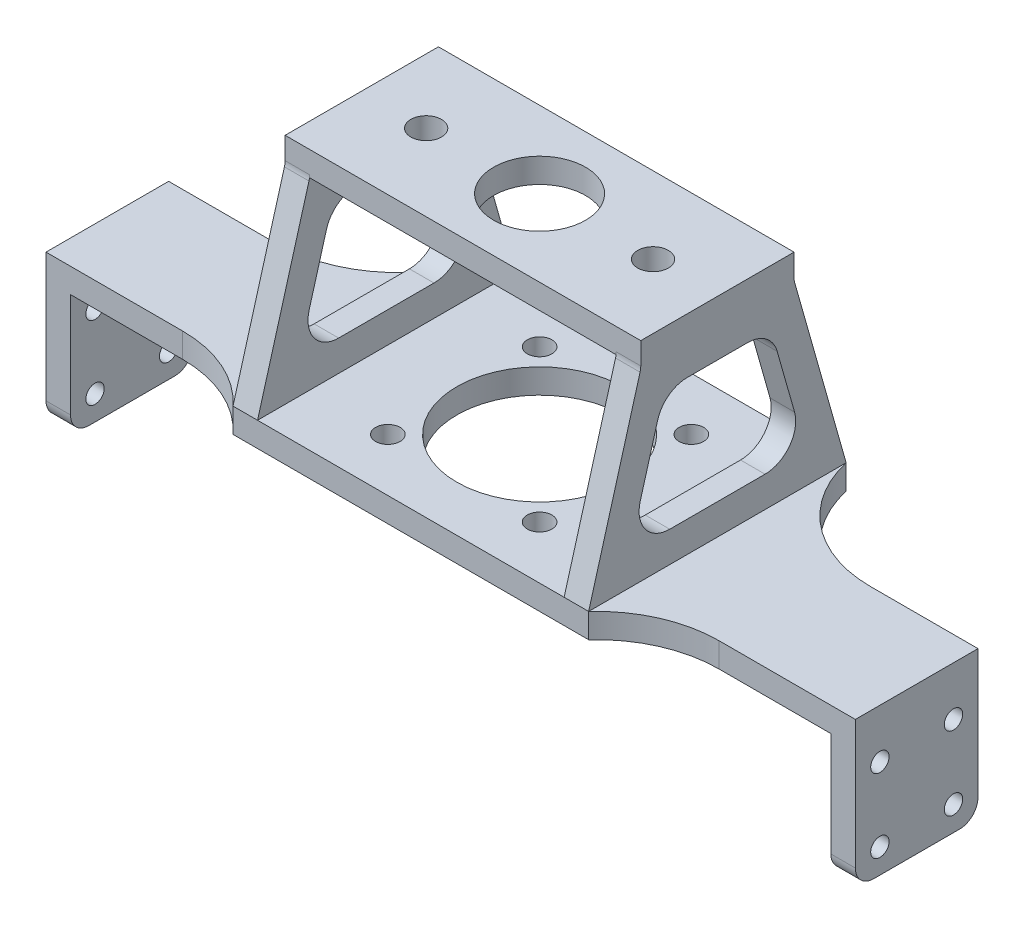
SolidWorks part; units mm, degrees
material "6061 合金"
ref_plane "前视基准面" through (0, 0, 0) normal (0, 0, 1) x (1, 0, 0)
ref_plane "上视基准面" through (0, 0, 0) normal (0, 1, 0) x (1, 0, 0)
ref_plane "右视基准面" through (0, 0, 0) normal (1, 0, 0) x (0, 0, -1)
sketch "草图1" plane through (0, 0, 0) normal (0, 1, 0) x (1, 0, 0)
  line L1 (-66, -21) -> (66, -21)
  line L2 (-66, -21) -> (-66, 21)
  line L3 (-66, 21) -> (66, 21)
  line L4 (66, -21) -> (66, 21)
  line L5 (-66, -21) -> (66, 21) construction
  line L6 (-66, 21) -> (66, -21) construction
  point P0 (0, 0)
  dimension "D1" = 132
  dimension "D2" = 42
extrude "凸台-拉伸1" add sketch "草图1" along normal blind 4
sketch "草图2" plane through (0, 4, 0) normal (0, 1, 0) x (1, 0, 0)
  line L0 (0, 0) -> (0, 17.5) construction
  line L1 (0, 0) -> (12.3744, 12.3744) construction
  circle A0 centre (0, 0) radius 17.5 construction
  circle A1 centre (12.3744, 12.3744) radius 2
  circle A2 centre (12.3744, -12.3744) radius 2
  circle A3 centre (-12.3744, -12.3744) radius 2
  circle A4 centre (-12.3744, 12.3744) radius 2
  circle A5 centre (0, 0) radius 13.5
  point P15 (0, 0)
  dimension "D1" = 35
  dimension "D2" = 4
  dimension "D5" = 27
  dimension "D3" = 45
  dimension "D4" = 4
extrude "切除-拉伸1" cut sketch "草图2" against normal blind 4
sketch "草图3" plane through (0, 4, 0) normal (0, 1, 0) x (1, 0, 0)
  line L0 (0, 21) -> (0, -21) construction
  line L1 (66, 21) -> (-66, 21) construction
  line L2 (-66, -21) -> (66, -21) construction
  line L3 (29, -21) -> (25, -21)
  line L4 (-29, 21) -> (-25, 21)
  line L5 (-29, 21) -> (-29, -21)
  line L6 (-29, -21) -> (-25, -21)
  line L7 (-25, 21) -> (-25, -21)
  line L8 (25, 21) -> (25, -21)
  line L9 (29, 21) -> (25, 21)
  line L10 (29, 21) -> (29, -21)
  dimension "D1" = 25
  dimension "D2" = 4
extrude "凸台-拉伸2" add sketch "草图3" along normal blind 30
sketch "草图4" plane through (0, 34, 0) normal (0, 1, 0) x (1, 0, 0)
  line L1 (-29, 21) -> (29, 21)
  line L2 (-29, 21) -> (-29, -21)
  line L3 (-29, -21) -> (29, -21)
  line L4 (29, 21) -> (29, -21)
extrude "凸台-拉伸3" add sketch "草图4" along normal blind 4
sketch "草图5" plane through (0, 0, 0) normal (0, -1, 0) x (1, 0, 0)
  line L0 (0, 21) -> (0, -21) construction
  line L1 (-66, 21) -> (66, 21) construction
  line L2 (66, -21) -> (-66, -21) construction
  line L3 (66, -21) -> (62, -21)
  line L8 (-66, 21) -> (-62, 21)
  line L9 (-66, 21) -> (-66, -21)
  line L10 (-66, -21) -> (-62, -21)
  line L11 (-62, 21) -> (-62, -21)
  line L12 (62, 21) -> (62, -21)
  line L13 (66, 21) -> (62, 21)
  line L14 (66, 21) -> (66, -21)
  dimension "D1" = 4
extrude "凸台-拉伸4" add sketch "草图5" along normal blind 20
sketch "草图6" plane through (0, 38, 0) normal (0, 1, 0) x (1, 0, 0)
  line L0 (0, 21) -> (0, -21) construction
  line L1 (29, 21) -> (-29, 21) construction
  line L2 (-29, -21) -> (29, -21) construction
  line L3 (-29, 0) -> (29, 0) construction
  line L4 (-29, 21) -> (-29, -21) construction
  line L5 (29, -21) -> (29, 21) construction
  circle A0 centre (0, 0) radius 7.5
  circle A1 centre (-18.5, 0) radius 2.5
  circle A2 centre (18.5, 0) radius 2.5
  dimension "D1" = 15
  dimension "D2" = 5
  dimension "D3" = 18.5
extrude "切除-拉伸2" cut sketch "草图6" against normal blind 4
sketch "草图7" plane through (-29, 0, 0) normal (-1, 0, 0) x (0, 0, 1)
  line L0 (0, 4) -> (0, 38) construction
  line L1 (-21, 4) -> (21, 4) construction
  line L2 (-21, 4) -> (-12.5, 34)
  line L5 (21, 34) -> (-21, 34) construction
  line L9 (-21, 38) -> (-21, 4)
  line L12 (-21, 38) -> (21, 38) construction
  line L14 (-21, 38) -> (-12.5, 38)
  line L15 (-12.5, 38) -> (-12.5, 34)
  line L16 (21, 38) -> (12.5, 38)
  line L17 (21, 38) -> (21, 4)
  line L18 (21, 4) -> (12.5, 34)
  line L19 (12.5, 38) -> (12.5, 34)
  dimension "D1" = 12.5
extrude "切除-拉伸3" cut sketch "草图7" against normal through all
fillet "圆角1" radius 3 4 edges at (27, 34, 12.5) (-27, 34, 12.5) (27, 34, -12.5) (-27, 34, -12.5)
sketch "草图8" plane through (0, 4, 0) normal (0, 1, 0) x (1, 0, 0)
  line L0 (-66, 0) -> (66, 0) construction
  line L1 (-66, 21) -> (-66, -21) construction
  line L2 (66, -21) -> (66, 21) construction
  line L3 (0, 21) -> (0, -21) construction
  line L4 (25, 21) -> (-25, 21) construction
  line L5 (-25, -21) -> (25, -21) construction
  line L6 (-66, 5.5) -> (-66, 21)
  line L7 (-66, 5.5) -> (-62, 5.5)
  line L8 (-62, 21) -> (-62, -21) construction
  line L9 (-62, 5.5) -> (-29, 5.5)
  line L10 (-29, 5.5) -> (-29, 21)
  line L11 (-29, 21) -> (-66, 21) construction
  line L13 (-66, 21) -> (-29, 21)
  line L19 (66, -14.5) -> (29, -14.5)
  line L21 (29, -14.5) -> (29, -21)
  line L22 (66, -21) -> (29, -21)
  line L23 (66, -14.5) -> (66, -21)
  line L24 (66, 5.5) -> (66, 21)
  line L25 (66, 5.5) -> (62, 5.5)
  line L26 (62, 5.5) -> (29, 5.5)
  line L27 (29, 5.5) -> (29, 21)
  line L28 (66, 21) -> (29, 21)
  line L30 (29, -12.6136) -> (29, -21) construction
  line L31 (29, -21) -> (66, -21) construction
  line L32 (29, -21) -> (29, 21) construction
  line L33 (-66, -14.5) -> (-66, -21)
  line L34 (-66, -21) -> (-29, -21)
  line L35 (-29, -14.5) -> (-29, -21)
  line L36 (-66, -14.5) -> (-29, -14.5)
  dimension "D1" = 5.5
  dimension "D2" = 14.5
extrude "切除-拉伸4" cut sketch "草图8" against normal blind 24
fillet "圆角2" radius 20 4 edges at (29, 2, 14.5) (29, 2, -5.5) (-29, 2, -5.5) (-29, 2, 14.5)
sketch "草图11" plane through (-29, 0, 0) normal (-1, 0, 0) x (0, 0, 1)
  line L19 (12.5, 34) -> (-12.5, 34) construction
  line L20 (12.6136, 33.599) -> (21, 4) construction
  line L21 (-21, 4) -> (-12.6136, 33.599) construction
  line L22 (12.5, 34) -> (-12.5, 34) construction
  line L23 (12.5, 34) -> (21, 4) construction
  line L24 (-21, 4) -> (-12.5, 34) construction
  line L25 (-21, 4) -> (21, 4) construction
  line L26 (8.7198, 29) -> (-8.7198, 29)
  line L27 (-14.3865, 9) -> (-8.7198, 29)
  line L28 (-14.3865, 9) -> (14.3865, 9)
  line L29 (8.7198, 29) -> (14.3865, 9)
  dimension "D1" = 5
extrude "切除-拉伸6" cut sketch "草图11" against normal through all
sketch "草图12" plane through (-66, 0, 0) normal (-1, 0, 0) x (0, 0, 1)
  line L0 (4.5, 0) -> (4.5, -20) construction
  line L6 (-5.5, 0) -> (14.5, 0) construction
  line L8 (-5.5, 0) -> (-5.5, -20) construction
  line L24 (-5.5, -20) -> (14.5, -20) construction
  line L25 (14.5, 0) -> (14.5, -20) construction
  line L26 (-5.5, -10) -> (14.5, -10) construction
  line L28 (-1.5, -16) -> (10.5, -16) construction
  line L29 (-1.5, -16) -> (-1.5, -4) construction
  line L30 (-1.5, -4) -> (10.5, -4) construction
  line L31 (10.5, -16) -> (10.5, -4) construction
  line L32 (-1.5, -16) -> (10.5, -4) construction
  line L33 (-1.5, -4) -> (10.5, -16) construction
  circle A4 centre (-1.5, -4) radius 1.5
  circle A5 centre (10.5, -4) radius 1.5
  circle A6 centre (10.5, -16) radius 1.5
  circle A7 centre (-1.5, -16) radius 1.5
  point P8 (4.5, -10)
  dimension "D3" = 3
  dimension "D1" = 12
  dimension "D2" = 12
extrude "切除-拉伸7" cut sketch "草图12" against normal through all and the other way through all
fillet "圆角5" radius 3 4 edges at (64, -20, 14.5) (64, -20, -5.5) (-64, -20, -5.5) (-64, -20, 14.5)
fillet "圆角6" radius 5 8 edges at (27, 29, -8.7198) (27, 9, -14.3865) (27, 9, 14.3865) (27, 29, 8.7198) (-27, 29, 8.7198) (-27, 29, -8.7198) (-27, 9, -14.3865) (-27, 9, 14.3865)
